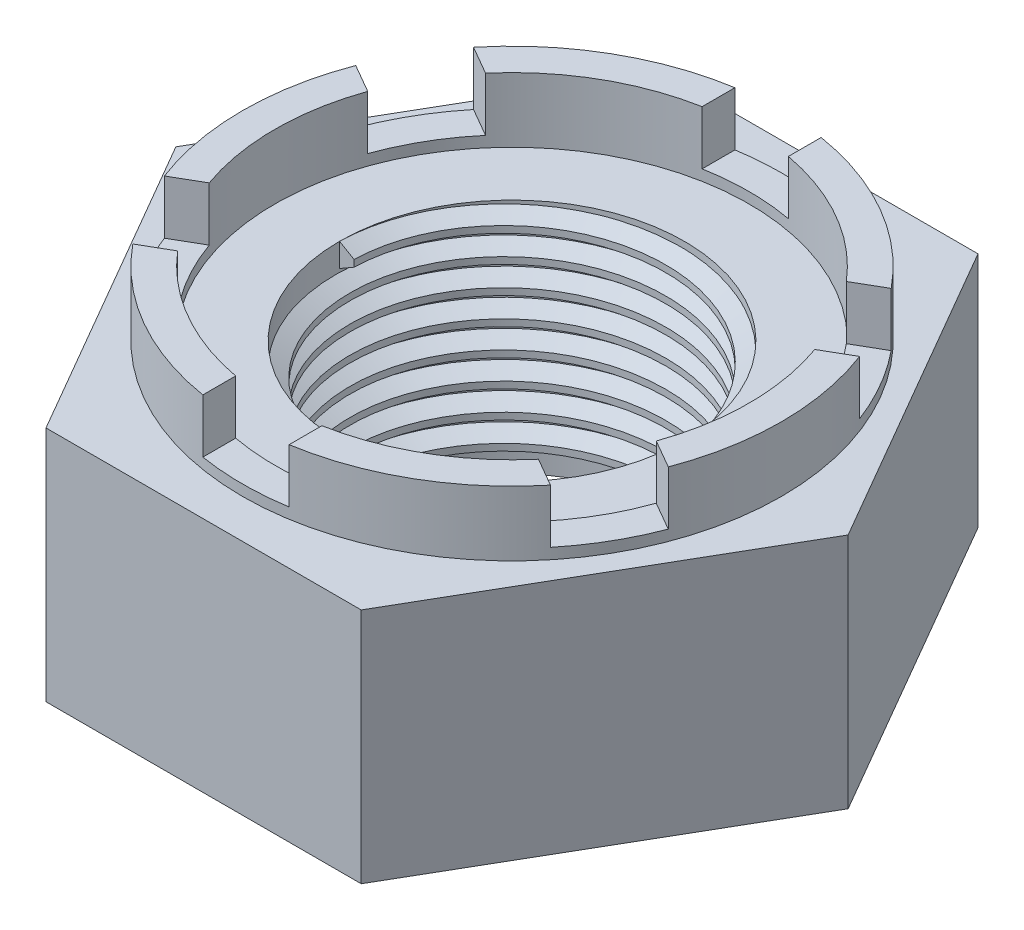
SolidWorks part; units mm, degrees
ref_plane "Front Plane" through (0, 0, 0) normal (0, 0, 1) x (1, 0, 0)
ref_plane "Top Plane" through (0, 0, 0) normal (0, 1, 0) x (1, 0, 0)
ref_plane "Right Plane" through (0, 0, 0) normal (1, 0, 0) x (0, 0, -1)
sketch "Sketch2" plane through (0, 0, 0) normal (0, 1, 0) x (1, 0, 0)
  line L0 (15.59, 0) -> (0, 0) construction
  line L1 (0, 0) -> (0, 16.5509) construction
  line L2 (-7.3096, 14.3042) -> (7.3096, 14.3042)
  line L3 (7.3096, 14.3042) -> (15.59, 0)
  line L4 (-7.3096, 14.3042) -> (-15.59, 0)
  line L5 (0, 0) -> (-15.59, 0) construction
  line L6 (-7.3096, -14.3042) -> (-15.59, 0)
  line L7 (-7.3096, -14.3042) -> (7.3096, -14.3042)
  line L8 (7.3096, -14.3042) -> (15.59, 0)
  circle A0 centre (0, 0) radius 8
  point P8 (0, 14.3042)
  dimension "D1" = 31.18
  dimension "D3" = 16
  dimension "D2" = 27
extrude "Boss-Extrude1" add sketch "Sketch2" along normal blind 11
thread "Thread2" pitch 1.25 method extrude profile "Thread Profile3" start angle 0, offset 0, length 10, pitch 1.25, diameter 16
ref_plane "Plane3" through (-8, 11, 0) normal (0, 0, 1) x (-1, 0, 0)
sketch "Thread Profile3" plane through (-8, 11, 0) normal (0, 0, 1) x (-1, 0, 0)
  line L0 (0, 0) -> (0, 1.25) construction
  line L11 (0, 0) -> (0, 1.0937)
  line L12 (0, 1.0937) -> (-0.6766, 0.7031)
  line L13 (-0.6766, 0.7031) -> (-0.6766, 0.3906)
  line L15 (-0.6766, 0.3906) -> (0, 0)
  line L17 (-0.6766, 0.5469) -> (0, 0.5469) construction
  point P2 (0, 0)
  dimension "Pitch" = 1.25
  dimension "Profile_Angle" = 60
  dimension "Profile_Land" = 0.3125
  dimension "Profile_Height" = 0.6766
sketch "Sketch11" plane through (0, 11, 0) normal (0, 1, 0) x (1, 0, 0)
  line L0 (0, 0) -> (0, 14.3042) construction
  line L1 (7.3096, 14.3042) -> (-7.3096, 14.3042) construction
  line L2 (0, 0) -> (15.59, 0) construction
  circle A0 centre (0, 0) radius 12.5
  circle A1 centre (0, 0) radius 11
  dimension "D1" = 25
  dimension "D2" = 22
extrude "Boss-Extrude2" add sketch "Sketch11" along normal blind 3
sketch "Sketch12" plane through (0, 14, 0) normal (0, 1, 0) x (1, 0, 0)
  line L0 (0, 0) -> (0, 16.0691) construction
  line L3 (-2, 12.8856) -> (2, 12.8856)
  line L4 (-2, 12.8856) -> (-2, 10.5635)
  line L5 (-2, 10.5635) -> (2, 10.5635)
  line L6 (2, 12.8856) -> (2, 10.5635)
  line L7 (-2, 12.8856) -> (2, 10.5635) construction
  line L8 (-2, 10.5635) -> (2, 12.8856) construction
  point P0 (0, 11.7245)
  point P8 (0, 0)
  dimension "D1" = 4
extrude "Cut-Extrude1" cut sketch "Sketch12" against normal blind 2.5
pattern_circular "CirPattern1" count 6 over 360 about axis through (0, 14, 0) along (0, 1, 0) of "Cut-Extrude1"
